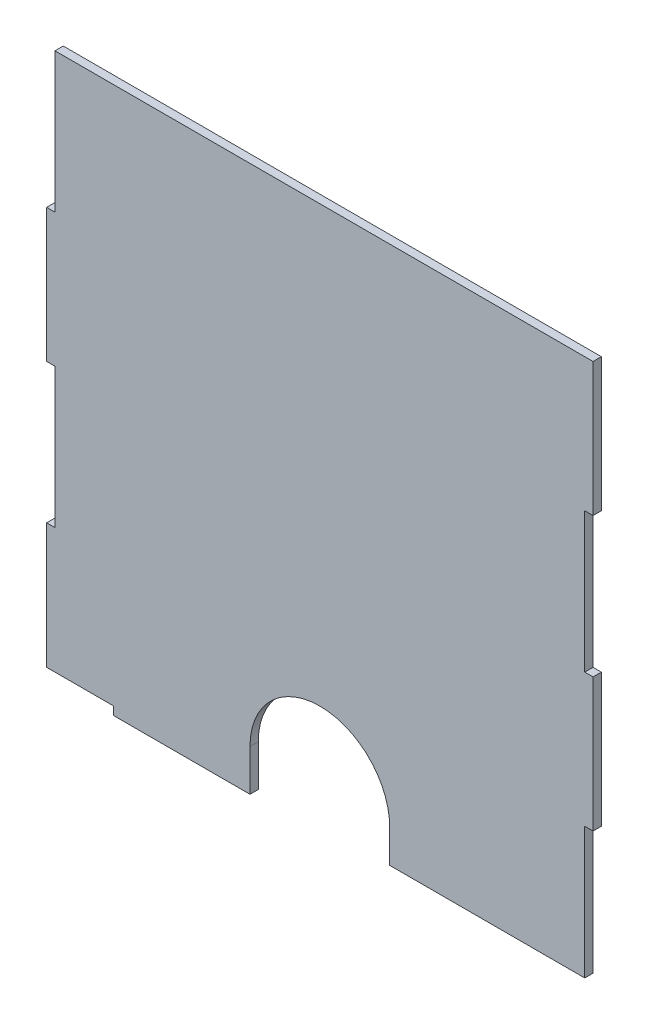
SolidWorks part; units mm, degrees
ref_plane "Front Plane" through (0, 0, 0) normal (0, 0, 1) x (1, 0, 0)
ref_plane "Top Plane" through (0, 0, 0) normal (0, 1, 0) x (1, 0, 0)
ref_plane "Right Plane" through (0, 0, 0) normal (1, 0, 0) x (0, 0, -1)
sketch "Sketch1" plane through (0, 0, 0) normal (0, 0, 1) x (1, 0, 0)
  line L0 (0, -197.5) -> (0, -167.5) construction
  line L1 (-197.5, -197.5) -> (197.5, -197.5)
  line L2 (-197.5, -197.5) -> (-197.5, 197.5)
  line L3 (-197.5, 197.5) -> (197.5, 197.5)
  line L4 (197.5, -197.5) -> (197.5, 197.5)
  line L5 (-197.5, -197.5) -> (197.5, 197.5) construction
  line L6 (-197.5, 197.5) -> (197.5, -197.5) construction
  line L7 (-50.5, -227.5) -> (50.5, -227.5)
  line L8 (-50.5, -227.5) -> (-50.5, -167.5)
  line L10 (50.5, -227.5) -> (50.5, -167.5)
  line L11 (-50.5, -227.5) -> (50.5, -167.5) construction
  line L12 (-50.5, -167.5) -> (50.5, -227.5) construction
  line L14 (-197.5, -197.5) -> (-149, -197.5)
  line L15 (-197.5, -197.5) -> (-197.5, -191.5)
  line L16 (-197.5, -191.5) -> (-149, -191.5)
  line L17 (-149, -197.5) -> (-149, -191.5)
  line L18 (-197.5, 197.5) -> (-191.5, 197.5)
  line L19 (-197.5, 197.5) -> (-197.5, 96.5)
  line L20 (-197.5, 96.5) -> (-191.5, 96.5)
  line L21 (-191.5, 197.5) -> (-191.5, 96.5)
  line L22 (197.5, -197.5) -> (191.5, -197.5)
  line L23 (197.5, -197.5) -> (197.5, -96.5)
  line L24 (197.5, -96.5) -> (191.5, -96.5)
  line L25 (191.5, -197.5) -> (191.5, -96.5)
  line L26 (-197.5, 0) -> (-191.5, 0)
  line L27 (-197.5, 0) -> (-197.5, -101)
  line L28 (-197.5, -101) -> (-191.5, -101)
  line L29 (-191.5, 0) -> (-191.5, -101)
  line L30 (197.5, 0) -> (191.5, 0)
  line L31 (197.5, 0) -> (197.5, 101)
  line L32 (197.5, 101) -> (191.5, 101)
  line L33 (191.5, 0) -> (191.5, 101)
  line L34 (48, -197.5) -> (191.5, -197.5)
  line L35 (48, -197.5) -> (48, -191.5)
  line L36 (48, -191.5) -> (191.5, -191.5)
  line L37 (191.5, -197.5) -> (191.5, -191.5)
  circle A0 centre (0, -167.5) radius 50.5
  point P0 (0, 0)
  point P6 (0, -197.5)
  dimension "D1" = 395
  dimension "D2" = 101
  dimension "D3" = 30
  dimension "D4" = 6
  dimension "D5" = 101
  dimension "D6" = 143.5
  dimension "D7" = 6
  dimension "D8" = 48.5
extrude "Boss-Extrude1" add sketch "Sketch1" along normal blind 6 contours A0 L10 L1 L25 L24 L4 L30 L33 L32 L3 L21 L20 L2 L26 L29 L28 L16 L17 L8 region at (-0.3572, 9.3466, 0)
